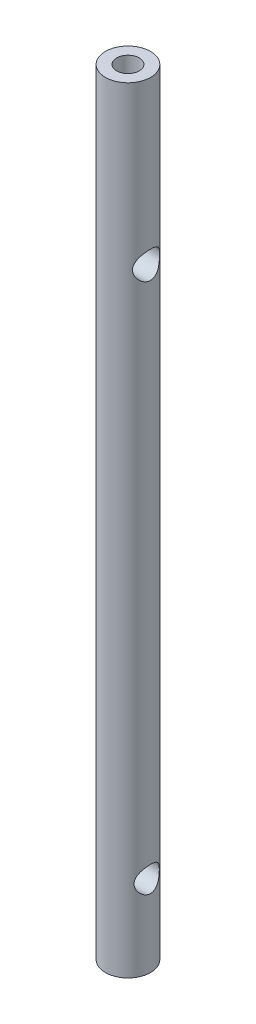
SolidWorks part; units mm, degrees
ref_plane "前视基准面" through (0, 0, 0) normal (0, 0, 1) x (1, 0, 0)
ref_plane "上视基准面" through (0, 0, 0) normal (0, 1, 0) x (1, 0, 0)
ref_plane "右视基准面" through (0, 0, 0) normal (1, 0, 0) x (0, 0, -1)
sketch "草图1" plane through (0, 0, 0) normal (0, 1, 0) x (1, 0, 0)
  circle A0 centre (0, 0) radius 2.5
extrude "凸台-拉伸1" add sketch "草图1" along normal blind 86
hole_wizard "M3 螺纹孔1" positions "草图6" profile "草图7" tap size "M3" standard "GB"
sketch "草图6" plane through (0, 0, 0) normal (0, -1, 0) x (-1, 0, 0)
  point P0 (0, 0)
sketch "草图7" plane through (0, 0, 0) normal (1, 0, 0) x (0, 0, -1)
  line L0 (0, 0) -> (0, 7.5)
  line L1 (0, 7.5) -> (1.25, 6.7489)
  line L2 (1.25, 6.7489) -> (1.25, 0)
  line L5 (1.25, 0) -> (0, 0)
  line L10 (0, 7.5) -> (-1.25, 6.7489) construction
  line L11 (0, -6.35) -> (0, 107.95) construction
  dimension "螺纹孔钻头直径" = 2.5
  dimension "螺纹孔钻头深度" = 7.5
  dimension "导头角度" = 118
cosmetic thread "孔螺蚊线2" parameters "D1"=6, "D2"=3
hole_wizard "M3 螺纹孔2" positions "草图8" profile "草图9" tap size "M3" standard "GB"
sketch "草图8" plane through (0, 86, 0) normal (0, 1, 0) x (1, 0, 0)
  point P0 (0, 0)
sketch "草图9" plane through (0, 86, 0) normal (1, 0, 0) x (0, 0, 1)
  line L0 (0, 0) -> (0, 7.5)
  line L1 (0, 7.5) -> (1.25, 6.7489)
  line L2 (1.25, 6.7489) -> (1.25, 0)
  line L5 (1.25, 0) -> (0, 0)
  line L10 (0, 7.5) -> (-1.25, 6.7489) construction
  line L11 (0, -6.35) -> (0, 107.95) construction
  dimension "螺纹孔钻头直径" = 2.5
  dimension "螺纹孔钻头深度" = 7.5
  dimension "导头角度" = 118
cosmetic thread "孔螺蚊线3" parameters "D1"=6, "D2"=3
sketch "草图10" plane through (0, 0, 0) normal (1, 0, 0) x (0, 0, -1)
  line L0 (2.5, 86) -> (-2.5, 86) construction
  line L1 (-2.5, 0) -> (2.5, 0) construction
  circle A0 centre (0, 68) radius 1.5
  circle A1 centre (0, 9) radius 1.4
  dimension "D1" = 18
  dimension "D2" = 9
extrude "切除-拉伸2" cut sketch "草图10" against normal blind 5 and the other way blind 5
